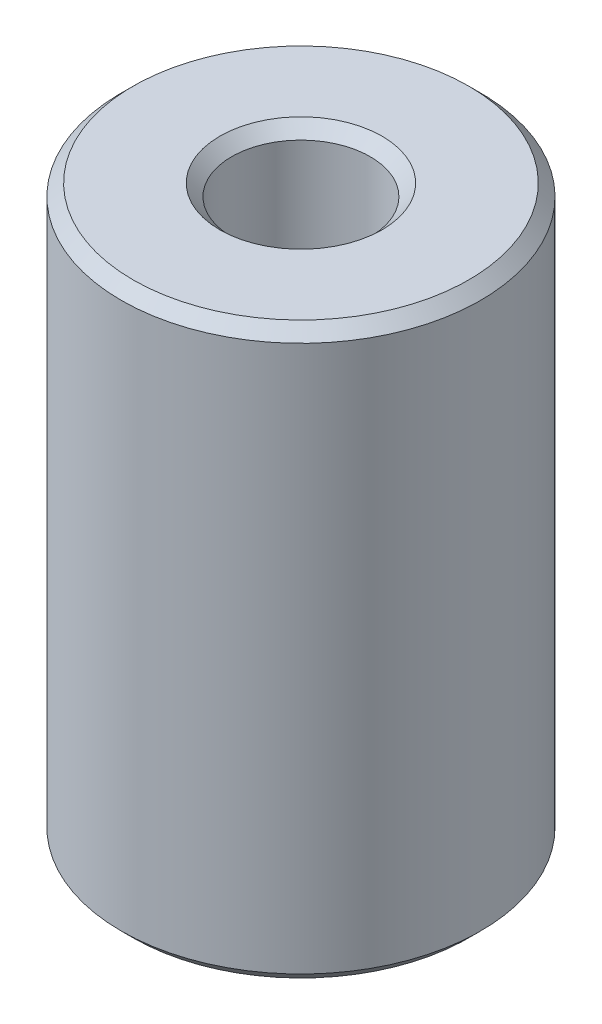
SolidWorks part; units mm, degrees
ref_plane "Front Plane" through (0, 0, 0) normal (0, 0, 1) x (1, 0, 0)
ref_plane "Top Plane" through (0, 0, 0) normal (0, 1, 0) x (1, 0, 0)
ref_plane "Right Plane" through (0, 0, 0) normal (1, 0, 0) x (0, 0, -1)
sketch "Sketch1" plane through (0, 0, 0) normal (0, 1, 0) x (1, 0, 0)
  circle A0 centre (0, 0) radius 55
  dimension "SLEEVE_OD" = 110
extrude "Boss-Extrude1" add sketch "Sketch1" along normal blind 174.4443
sketch "Sketch2" plane through (0, 0, 0) normal (0, 1, 0) x (1, 0, 0)
  circle A0 centre (0, 0) radius 21.221
  dimension "BORE_D" = 42.4421
extrude "Cut-Extrude1" cut sketch "Sketch2" along normal through all
chamfer "Chamfer1" distance 3.6183 angle 45 4 edges at (0, 174.4443, 21.221) (0, 0, 21.221) (0, 0, 55) (0, 174.4443, 55)
